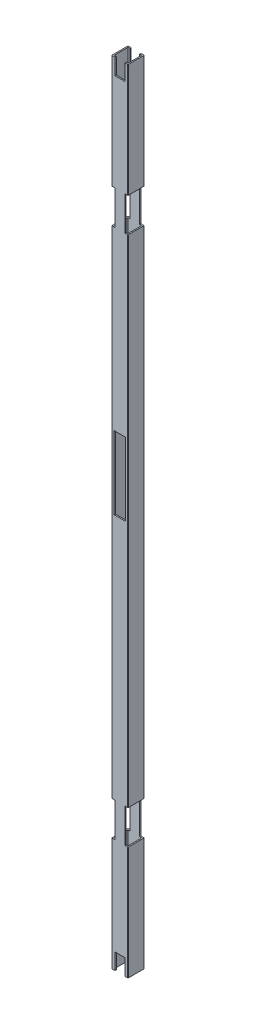
SolidWorks part; units mm, degrees
ref_plane "Front Plane" through (0, 0, 0) normal (0, 0, 1) x (1, 0, 0)
ref_plane "Top Plane" through (0, 0, 0) normal (0, 1, 0) x (1, 0, 0)
ref_plane "Right Plane" through (0, 0, 0) normal (1, 0, 0) x (0, 0, -1)
sketch "Sketch1" plane through (0, 0, 0) normal (0, 1, 0) x (1, 0, 0)
  line L0 (1.5, 1.5) -> (18.5, 1.5)
  line L1 (0.5, 0) -> (19.5, 0)
  line L2 (0, 0.5) -> (0, 19.5)
  line L3 (0.5, 20) -> (19.5, 20)
  line L4 (20, 0.5) -> (20, 19.5)
  line L5 (18.5, 1.5) -> (18.5, 18.5)
  line L6 (1.5, 18.5) -> (18.5, 18.5)
  line L7 (1.5, 1.5) -> (1.5, 18.5)
  arc A0 (19.5, 0) -> (20, 0.5) centre (19.5, 0.5) ccw
  arc A1 (0.5, 0) -> (0, 0.5) centre (0.5, 0.5) cw
  arc A2 (0, 19.5) -> (0.5, 20) centre (0.5, 19.5) cw
  arc A3 (19.5, 20) -> (20, 19.5) centre (19.5, 19.5) cw
  arc A4 (18.5, 1.5) -> (18.5, 1.5) centre (18.5, 1.5) ccw
  arc A5 (18.5, 18.5) -> (18.5, 18.5) centre (18.5, 18.5) cw
  arc A6 (1.5, 18.5) -> (1.5, 18.5) centre (1.5, 18.5) cw
  arc A7 (1.5, 1.5) -> (1.5, 1.5) centre (1.5, 1.5) cw
  point P9 (0, 0)
  dimension "D3" = 0.5
  dimension "D1" = 20
  dimension "D2" = 20
  dimension "D4" = 1.5
extrude "Boss-Extrude1" add sketch "Sketch1" along normal blind 977
sketch "Sketch2" plane through (0, 0, 0) normal (0, 0, 1) x (1, 0, 0)
  line L0 (0.5, 977) -> (19.5, 977) construction
  line L1 (16, 977) -> (4, 977)
  line L2 (16, 977) -> (16, 957)
  line L3 (16, 957) -> (4, 957)
  line L4 (4, 977) -> (4, 957)
  line L5 (20, 977) -> (20, 0) construction
  point P8 (10, 977)
  point P9 (10, 977)
  dimension "D1" = 20
  dimension "D2" = 4
extrude "Cut-Extrude1" cut sketch "Sketch2" against normal blind 1177
sketch "Sketch3" plane through (0, 0, -20) normal (0, 0, -1) x (-1, 0, 0)
  line L0 (0, 977) -> (0, 0) construction
  line L1 (0, 837) -> (-4, 837)
  line L2 (0, 837) -> (0, 794.8)
  line L3 (0, 794.8) -> (-4, 794.8)
  line L4 (-4, 837) -> (-4, 794.8)
  line L5 (-20, 977) -> (-20, 0) construction
  line L6 (-20, 837) -> (-16, 837)
  line L7 (-20, 837) -> (-20, 794.8)
  line L8 (-20, 794.8) -> (-16, 794.8)
  line L9 (-16, 837) -> (-16, 794.8)
  line L10 (-4, 977) -> (-0.5, 977) construction
  point P14 (-2, 837)
  dimension "D1" = 4
  dimension "D2" = 140
  dimension "D3" = 42.2
extrude "Cut-Extrude2" cut sketch "Sketch3" against normal blind 1177
ref_plane "Plane1" through (0, 488.5, 0) normal (0, 1, 0) x (1, 0, 0)
mirror "Mirror1" about plane through (0, 488.5, 0) normal (0, 1, 0) of "Cut-Extrude2", "Cut-Extrude1"
sketch "Sketch4" plane through (0, 0, -20) normal (0, 0, 1) x (1, 0, 0)
  line L1 (19.5, 977) -> (19.5, 837) construction
  line L3 (16, 977) -> (19.5, 977) construction
  circle A0 centre (7.75, 923.65) radius 2.1
  circle A1 centre (7.75, 877.35) radius 2.1
  dimension "D1" = 46.3
  dimension "D2" = 53.35
  dimension "D3" = 11.75
  dimension "D4" = 4.2
extrude "Cut-Extrude3" [suppressed] cut sketch "Sketch4" along normal blind 10
sketch "Sketch6" plane through (20, 0, 0) normal (1, 0, 0) x (0, 0, -1)
  line L0 (0, 977) -> (0, 837) construction
  line L1 (0, 933.65) -> (4, 933.65)
  line L2 (0, 933.65) -> (0, 867.35)
  line L3 (0, 867.35) -> (4, 867.35)
  line L4 (4, 933.65) -> (4, 867.35)
  line L5 (0.5, 977) -> (19.5, 977) construction
  dimension "D1" = 43.35
  dimension "D2" = 4
  dimension "D3" = 66.3
extrude "Cut-Extrude4" [suppressed] cut sketch "Sketch6" along normal blind 15 from offset 20 offset against normal yes
sketch "Sketch7" plane through (0, 0, 0) normal (0, 0, 1) x (1, 0, 0)
  line L0 (16, 977) -> (19.5, 977) construction
  line L1 (17, 577) -> (3, 577)
  line L2 (17, 577) -> (17, 487)
  line L3 (17, 487) -> (3, 487)
  line L4 (3, 577) -> (3, 487)
  line L5 (20, 794.8) -> (20, 182.2) construction
  line L6 (0, 794.8) -> (0, 182.2) construction
  dimension "D1" = 400
  dimension "D2" = 3
  dimension "D3" = 3
  dimension "D4" = 90
extrude "Cut-Extrude5" cut sketch "Sketch7" against normal blind 10
sketch "Sketch8" plane through (0, 0, -18.5) normal (0, 0, 1) x (1, 0, 0)
  line L0 (17, 532) -> (3, 532) construction
  line L1 (17, 487) -> (17, 577) construction
  line L2 (3, 577) -> (3, 487) construction
  line L3 (17, 577) -> (3, 577) construction
  circle A0 centre (10, 567) radius 2.5
  circle A1 centre (10, 497) radius 2.5
  dimension "D1" = 5
  dimension "D2" = 10
extrude "Cut-Extrude6" cut sketch "Sketch8" against normal blind 10
